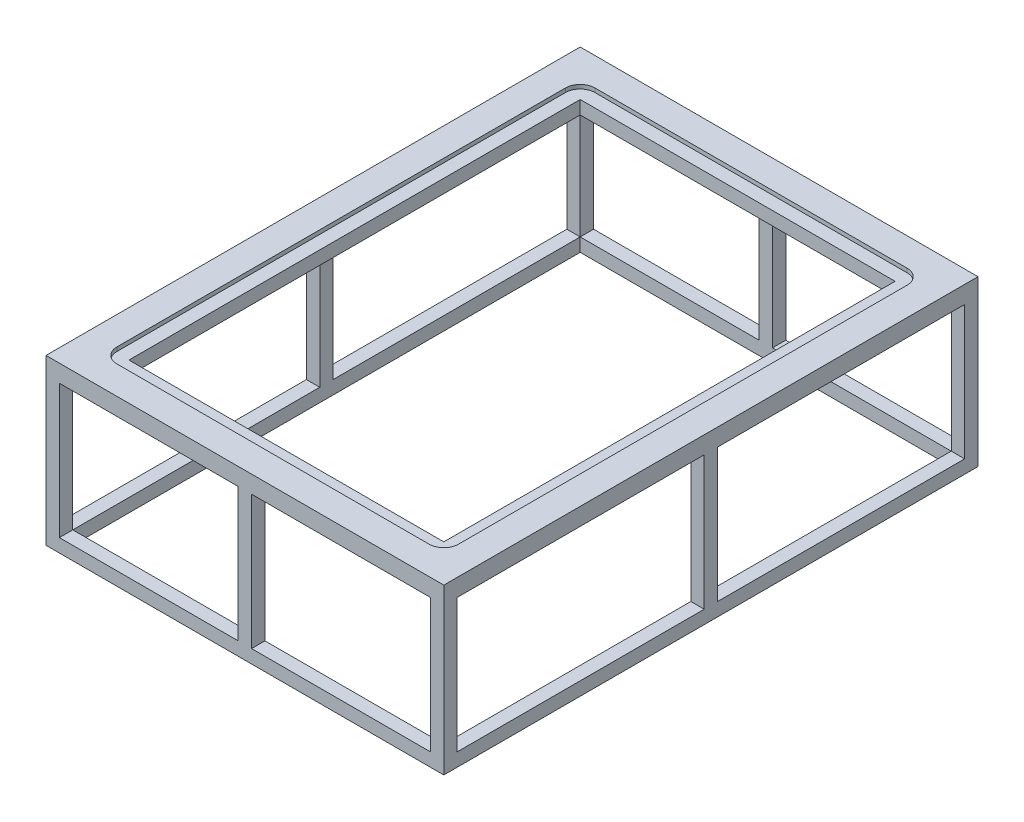
SolidWorks part; units mm, degrees
ref_plane "Front Plane" through (0, 0, 0) normal (0, 0, 1) x (1, 0, 0)
ref_plane "Top Plane" through (0, 0, 0) normal (0, 1, 0) x (1, 0, 0)
ref_plane "Right Plane" through (0, 0, 0) normal (1, 0, 0) x (0, 0, -1)
sketch "Sketch1" plane through (0, 0, 0) normal (0, 1, 0) x (1, 0, 0)
  line L1 (0, 0) -> (253.5, 0)
  line L2 (0, 0) -> (0, 355.5)
  line L3 (0, 355.5) -> (253.5, 355.5)
  line L4 (253.5, 0) -> (253.5, 355.5)
  line L5 (-22, 377.5) -> (275.5, 377.5)
  line L6 (-22, 377.5) -> (-22, -22)
  line L7 (-22, -22) -> (275.5, -22)
  line L8 (275.5, 377.5) -> (275.5, -22)
  line L9 (-12, 367.5) -> (265.5, 367.5)
  line L10 (-12, 367.5) -> (-12, -12)
  line L11 (-12, -12) -> (265.5, -12)
  line L12 (265.5, 367.5) -> (265.5, -12)
  dimension "D1" = 253.5
  dimension "D2" = 355.5
  dimension "D3" = 22
  dimension "D4" = 22
  dimension "D5" = 22
  dimension "D6" = 22
  dimension "D7" = 10
  dimension "D8" = 10
  dimension "D9" = 10
  dimension "D10" = 10
extrude "Boss-Extrude1" add sketch "Sketch1" along normal blind 10 contours L8 L5 L6 L7 L9 L12 L11 L10 region at (126.75, 0, -372.519)
sketch "Sketch2" plane through (0, 10, 0) normal (0, 1, 0) x (1, 0, 0)
  line L0 (-22, -22) -> (275.5, -22) construction
  line L1 (131.75, -22) -> (121.75, -22)
  line L2 (131.75, -22) -> (131.75, -12)
  line L3 (131.75, -12) -> (121.75, -12)
  line L4 (121.75, -22) -> (121.75, -12)
  line L5 (-12, -12) -> (265.5, -12) construction
  line L6 (-12, 367.5) -> (265.5, 367.5) construction
  line L7 (275.5, -22) -> (265.5, -22)
  line L8 (275.5, -22) -> (275.5, -12)
  line L9 (275.5, -12) -> (265.5, -12)
  line L10 (265.5, -22) -> (265.5, -12)
  line L11 (-22, -22) -> (-12, -22)
  line L12 (-22, -22) -> (-22, -12)
  line L13 (-22, -12) -> (-12, -12)
  line L14 (-12, -22) -> (-12, -12)
  line L15 (-22, 377.5) -> (-12, 377.5)
  line L16 (-22, 377.5) -> (-22, 367.5)
  line L17 (-22, 367.5) -> (-12, 367.5)
  line L18 (-12, 377.5) -> (-12, 367.5)
  line L19 (275.5, 377.5) -> (265.5, 377.5)
  line L20 (275.5, 377.5) -> (275.5, 367.5)
  line L21 (275.5, 367.5) -> (265.5, 367.5)
  line L22 (265.5, 377.5) -> (265.5, 367.5)
  line L23 (131.75, 367.5) -> (121.75, 367.5)
  line L24 (131.75, 367.5) -> (131.75, 377.5)
  line L25 (131.75, 377.5) -> (121.75, 377.5)
  line L26 (121.75, 367.5) -> (121.75, 377.5)
  line L27 (-22, 377.5) -> (275.5, 377.5) construction
  line L28 (275.5, 377.5) -> (275.5, -22) construction
  line L29 (275.5, 172.75) -> (265.5, 172.75)
  line L30 (275.5, 172.75) -> (275.5, 182.75)
  line L31 (275.5, 182.75) -> (265.5, 182.75)
  line L32 (265.5, 172.75) -> (265.5, 182.75)
  line L33 (265.5, 367.5) -> (265.5, -12) construction
  line L34 (-12, 367.5) -> (-12, -12) construction
  line L35 (-12, 172.75) -> (-22, 172.75)
  line L36 (-12, 172.75) -> (-12, 182.75)
  line L37 (-12, 182.75) -> (-22, 182.75)
  line L38 (-22, 172.75) -> (-22, 182.75)
  line L39 (-22, 377.5) -> (-22, -22) construction
  dimension "D1" = 133.75
  dimension "D2" = 10
  dimension "D3" = 133.75
  dimension "D4" = 10
  dimension "D5" = 133.75
  dimension "D6" = 10
  dimension "D7" = 184.75
  dimension "D8" = 184.75
  dimension "D9" = 10
  dimension "D10" = 184.75
extrude "Boss-Extrude2" add sketch "Sketch2" along normal blind 100
sketch "Sketch3" plane through (0, 110, 0) normal (0, 1, 0) x (1, 0, 0)
  line L1 (-22, 377.5) -> (275.5, 377.5)
  line L2 (-22, 377.5) -> (-22, -22)
  line L3 (-22, -22) -> (275.5, -22)
  line L4 (275.5, 377.5) -> (275.5, -22)
  line L9 (244.5, 346.5) -> (9, 346.5)
  line L10 (244.5, 346.5) -> (244.5, 9)
  line L11 (244.5, 9) -> (9, 9)
  line L12 (9, 346.5) -> (9, 9)
  dimension "D1" = 235.5
  dimension "D2" = 337.5
  dimension "D3" = 31
  dimension "D4" = 31
  dimension "D5" = 31
  dimension "D6" = 31
extrude "Boss-Extrude3" add sketch "Sketch3" along normal blind 10
sketch "Sketch4" plane through (0, 0, 0) normal (0, -1, 0) x (1, 0, 0)
  line L0 (-22, -177.75) -> (275.5, -177.75)
  line L1 (-22, -377.5) -> (-22, 22) construction
  line L2 (275.5, -377.5) -> (275.5, 22) construction
  line L3 (126.75, -377.5) -> (126.75, 22)
  line L4 (-22, -377.5) -> (275.5, -377.5) construction
  line L5 (-22, 22) -> (275.5, 22) construction
  line L6 (-17, -377.5) -> (-17, 22)
  line L7 (-22, -377.5) -> (275.5, -377.5)
  line L8 (-22, -377.5) -> (-22, -367.5)
  line L9 (-22, -367.5) -> (275.5, -367.5)
  line L10 (275.5, -377.5) -> (275.5, -367.5)
  line L11 (-22, 22) -> (275.5, 22)
  line L12 (-22, 22) -> (-22, 12)
  line L13 (-22, 12) -> (275.5, 12)
  line L14 (275.5, 22) -> (275.5, 12)
  line L15 (275.5, -377.5) -> (265.5, -377.5)
  line L16 (275.5, -377.5) -> (275.5, 22)
  line L17 (275.5, 22) -> (265.5, 22)
  line L18 (265.5, -377.5) -> (265.5, 22)
  line L19 (-22, -377.5) -> (-12, -377.5)
  line L20 (-22, -377.5) -> (-22, 22)
  line L21 (-22, 22) -> (-12, 22)
  line L22 (-12, -377.5) -> (-12, 22)
  line L23 (-22, 17) -> (275.5, 17)
  line L24 (-22, -372.5) -> (275.5, -372.5)
  line L25 (265.5, -367.5) -> (275.5, -377.5)
  line L26 (265.5, 12) -> (275.5, 22)
  line L27 (-22, -377.5) -> (-12, -367.5)
  line L28 (-12, 12) -> (-22, 22)
  circle A0 centre (270.5, 17) radius 1.6
  circle A1 centre (270.5, -177.75) radius 1.6
  circle A2 centre (270.5, -372.5) radius 1.6
  circle A3 centre (126.75, -372.5) radius 1.6
  circle A4 centre (-17, -372.5) radius 1.6
  circle A5 centre (-17, -177.75) radius 1.6
  circle A6 centre (-17, 17) radius 1.6
  circle A7 centre (126.75, 17) radius 1.6
  dimension "D1" = 3.2
  dimension "D2" = 3.2
  dimension "D3" = 3.2
  dimension "D4" = 3.2
  dimension "D5" = 3.2
  dimension "D6" = 3.2
  dimension "D7" = 3.2
  dimension "D8" = 3.2
extrude "Cut-Extrude1" cut sketch "Sketch4" against normal blind 1.2 contours L26 A0 L23 | L26 A0 L23 | L23 A0 L26 | L23 A0 L26 | L0 A1 | L0 A1 | L24 A2 L25 | L25 A2 L24 | L25 A2 L24 | L24 A2 L25 | L23 A7 L3 | L3 A7 L23 | L3 A7 L23 | L23 A7 L3 | L24 A3 L3 | L3 A3 L24 | L24 A3 L3 | L3 A3 L24 | L23 A6 L6 | L6 A6 L28 | L28 A6 L23 | L23 A6 L6 | L28 A6 L23 | L6 A6 L28 | L0 A5 L6 | L6 A5 L0 | L0 A5 L6 | L6 A5 L0 | L24 A4 L27 | L27 A4 L6 | L6 A4 L24 | L24 A4 L27 | L27 A4 L6 | L6 A4 L24 region at (270.5, 0, -178.4291) region at (270.5, 0, -177.0709) region at (270.8201, 0, -371.7272) region at (269.5397, 0, -372.1022) region at (271.4603, 0, -372.8978) region at (269.5397, 0, 16.6022) region at (270.8201, 0, 16.2272) region at (271.4603, 0, 17.3978) region at (127.4291, 0, -371.8209) region at (126.0709, 0, -371.8209) region at (127.4291, 0, -373.1791) region at (270.1799, 0, -373.2728) region at (126.0709, 0, 16.3209) region at (127.4291, 0, 16.3209) region at (127.4291, 0, 17.6791) region at (270.1799, 0, 17.7728) region at (-16.3209, 0, -178.4291) region at (-16.3209, 0, -177.0709) region at (126.0709, 0, -373.1791) region at (-16.0397, 0, -372.1022) region at (-16.6022, 0, -371.5397) region at (126.0709, 0, 17.6791) region at (-16.6022, 0, 16.0397) region at (-16.0397, 0, 16.6022) region at (-17.6791, 0, -178.4291) region at (-17.6791, 0, -177.0709) region at (-17.6791, 0, -371.8209) region at (-16.3209, 0, -373.1791) region at (-17.9603, 0, -372.8978) region at (-17.3978, 0, -373.4603) region at (-17.6791, 0, 16.3209) region at (-16.3209, 0, 17.6791) region at (-17.3978, 0, 17.9603) region at (-17.9603, 0, 17.3978)
sketch "Sketch6" plane through (0, 120, 0) normal (0, 1, 0) x (1, 0, 0)
  line L0 (253.5, 10) -> (253.5, 345.5) construction
  line L1 (10, 0) -> (243.5, 0) construction
  line L2 (0, 345.5) -> (0, 10) construction
  line L3 (243.5, 355.5) -> (10, 355.5) construction
  line L4 (253.5, 10) -> (253.5, 345.5)
  line L5 (10, 0) -> (243.5, 0)
  line L6 (0, 345.5) -> (0, 10)
  line L7 (243.5, 355.5) -> (10, 355.5)
  line L8 (254.5, 10) -> (254.5, 345.5)
  line L9 (243.5, 356.5) -> (10, 356.5)
  line L10 (-1, 345.5) -> (-1, 10)
  line L11 (10, -1) -> (243.5, -1)
  line L13 (275.5, 377.5) -> (-22, 377.5)
  line L14 (275.5, 377.5) -> (275.5, -22)
  line L15 (275.5, -22) -> (-22, -22)
  line L16 (-22, 377.5) -> (-22, -22)
  circle A0 centre (247.5, 349.5) radius 1.6 construction
  circle A1 centre (247.5, 263.625) radius 1.6 construction
  circle A2 centre (247.5, 177.75) radius 1.6 construction
  circle A3 centre (247.5, 91.875) radius 1.6 construction
  circle A4 centre (247.5, 6) radius 1.6 construction
  circle A5 centre (167, 6) radius 1.6 construction
  circle A6 centre (86.5, 6) radius 1.6 construction
  circle A7 centre (6, 6) radius 1.6 construction
  circle A8 centre (6, 91.875) radius 1.6 construction
  circle A9 centre (6, 177.75) radius 1.6 construction
  circle A10 centre (6, 263.625) radius 1.6 construction
  circle A11 centre (6, 349.5) radius 1.6 construction
  circle A12 centre (167, 349.5) radius 1.6 construction
  circle A13 centre (86.5, 349.5) radius 1.6 construction
  circle A14 centre (247.5, 349.5) radius 1.6
  circle A15 centre (247.5, 263.625) radius 1.6
  circle A16 centre (247.5, 177.75) radius 1.6
  circle A17 centre (247.5, 91.875) radius 1.6
  circle A18 centre (247.5, 6) radius 1.6
  circle A19 centre (167, 6) radius 1.6
  circle A20 centre (86.5, 6) radius 1.6
  circle A21 centre (6, 6) radius 1.6
  circle A22 centre (6, 91.875) radius 1.6
  circle A23 centre (6, 177.75) radius 1.6
  circle A24 centre (6, 263.625) radius 1.6
  circle A25 centre (6, 349.5) radius 1.6
  circle A26 centre (167, 349.5) radius 1.6
  circle A27 centre (86.5, 349.5) radius 1.6
  arc A28 (253.5, 345.5) -> (243.5, 355.5) centre (243.5, 345.5) ccw construction
  arc A29 (243.5, 0) -> (253.5, 10) centre (243.5, 10) ccw construction
  arc A30 (0, 10) -> (10, 0) centre (10, 10) ccw construction
  arc A31 (10, 355.5) -> (0, 345.5) centre (10, 345.5) ccw construction
  arc A32 (253.5, 345.5) -> (243.5, 355.5) centre (243.5, 345.5) ccw
  arc A33 (243.5, 0) -> (253.5, 10) centre (243.5, 10) ccw
  arc A34 (0, 10) -> (10, 0) centre (10, 10) ccw
  arc A35 (10, 355.5) -> (0, 345.5) centre (10, 345.5) ccw
  arc A36 (254.5, 345.5) -> (243.5, 356.5) centre (243.5, 345.5) ccw
  arc A37 (10, 356.5) -> (-1, 345.5) centre (10, 345.5) ccw
  arc A38 (-1, 10) -> (10, -1) centre (10, 10) ccw
  arc A39 (243.5, -1) -> (254.5, 10) centre (243.5, 10) ccw
  line M9 (-22, 377.5) -> (-22, -22)
  line M10 (-22, -22) -> (275.5, -22)
  line M11 (275.5, -22) -> (275.5, 377.5)
  line M12 (275.5, 377.5) -> (-22, 377.5)
  dimension "D1" = 1
extrude "Boss-Extrude4" add sketch "Sketch6" along normal up to surface (3 mm away) contours A39 L11 A38 L10 A37 L9 A36 L8 M12 M9 M10 M11 region at (270.519, 120, -177.75)
